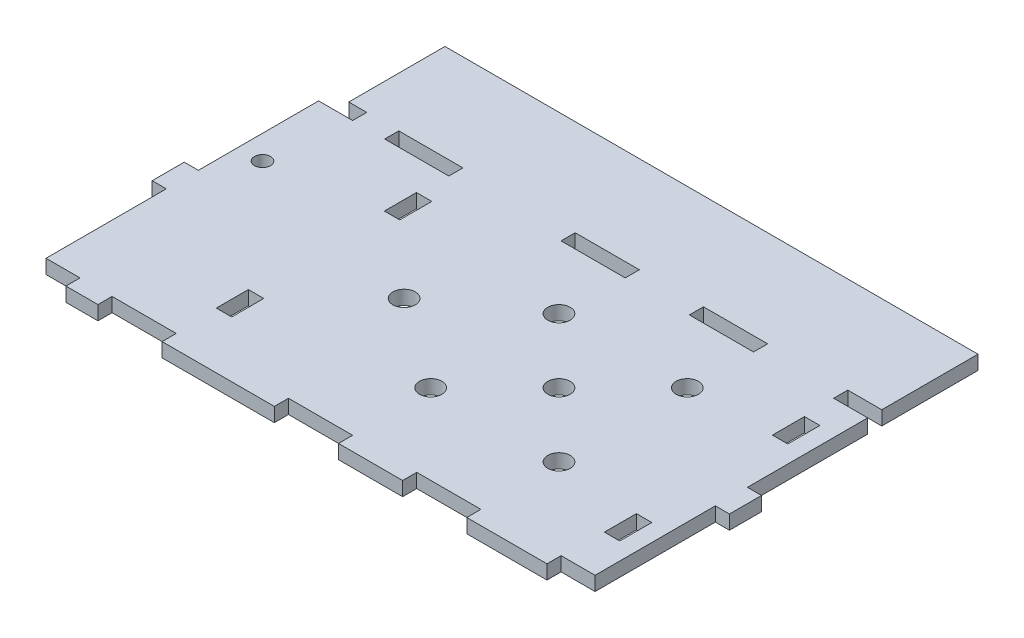
SolidWorks part; units mm, degrees
ref_plane "Front Plane" through (0, 0, 0) normal (0, 0, 1) x (1, 0, 0)
ref_plane "Top Plane" through (0, 0, 0) normal (0, 1, 0) x (1, 0, 0)
ref_plane "Right Plane" through (0, 0, 0) normal (1, 0, 0) x (0, 0, -1)
sketch "Sketch1" plane through (0, 0, 0) normal (0, 1, 0) x (1, 0, 0)
  line L0 (-108.712, 6.35) -> (-114.3, 6.35)
  line L2 (-108.712, -53.975) -> (-108.712, -6.35)
  line L4 (108.712, -53.975) -> (108.712, -6.35)
  line L5 (-108.712, -53.975) -> (108.712, 53.975) construction
  line L6 (-108.712, 53.975) -> (108.712, -53.975) construction
  line L7 (-114.3, 6.35) -> (-114.3, -6.35)
  line L8 (-114.3, -6.35) -> (-108.712, -6.35)
  line L9 (-108.712, 6.35) -> (-108.712, 53.975)
  line L10 (0, 60.325) -> (0, -60.325) construction
  line L11 (114.3, -6.35) -> (108.712, -6.35)
  line L12 (114.3, 6.35) -> (114.3, -6.35)
  line L13 (108.712, 6.35) -> (114.3, 6.35)
  line L14 (108.712, 6.35) -> (108.712, 53.975)
  line L23 (-108.712, 0) -> (106.818, 0) construction
  line L32 (-108.712, 53.975) -> (-95.25, 53.975)
  line L33 (-108.712, -53.975) -> (-95.25, -53.975)
  line L34 (-82.55, 53.975) -> (-57.15, 53.975)
  line L36 (-95.25, 53.975) -> (-95.25, 59.563)
  line L38 (-82.55, 53.975) -> (-82.55, 59.563)
  line L40 (-57.15, 53.975) -> (-57.15, 59.563)
  line L42 (-12.7, 53.975) -> (-12.7, 59.563)
  line L44 (12.7, 53.975) -> (12.7, 59.563)
  line L46 (38.1, 53.975) -> (38.1, 59.563)
  line L48 (63.5, 53.975) -> (63.5, 59.563)
  line L50 (95.25, 53.975) -> (95.25, 59.563)
  line L51 (-12.7, 53.975) -> (12.7, 53.975)
  line L52 (38.1, 53.975) -> (63.5, 53.975)
  line L53 (95.25, 53.975) -> (108.712, 53.975)
  line L54 (95.25, -53.975) -> (95.25, -59.563)
  line L55 (63.5, -59.563) -> (95.25, -59.563)
  line L56 (63.5, -53.975) -> (63.5, -59.563)
  line L57 (38.1, -53.975) -> (38.1, -59.563)
  line L58 (12.7, -59.563) -> (38.1, -59.563)
  line L59 (12.7, -53.975) -> (12.7, -59.563)
  line L60 (-12.7, -53.975) -> (-12.7, -59.563)
  line L61 (-57.15, -59.563) -> (-12.7, -59.563)
  line L62 (-57.15, -53.975) -> (-57.15, -59.563)
  line L63 (-82.55, -53.975) -> (-82.55, -59.563)
  line L64 (-95.25, -59.563) -> (-82.55, -59.563)
  line L65 (-95.25, -53.975) -> (-95.25, -59.563)
  line L66 (-82.55, -53.975) -> (-57.15, -53.975)
  line L67 (-12.7, -53.975) -> (12.7, -53.975)
  line L68 (38.1, -53.975) -> (63.5, -53.975)
  line L69 (95.25, -53.975) -> (108.712, -53.975)
  line L70 (95.25, 59.563) -> (108.712, 59.563)
  line L71 (108.712, 59.563) -> (108.712, 97.663)
  line L72 (-95.25, 59.563) -> (-102.362, 59.563)
  line L73 (-102.362, 59.563) -> (-102.362, 97.663)
  line L74 (-102.362, 97.663) -> (108.712, 97.663)
  line L75 (63.5, 59.563) -> (38.1, 59.563)
  line L76 (12.7, 59.563) -> (-12.7, 59.563)
  line L77 (-57.15, 59.563) -> (-82.55, 59.563)
  point P0 (0, 0)
  dimension "D1" = 107.95
  dimension "D2" = 217.424
  dimension "D3" = 12.7
  dimension "D4" = 5.588
  dimension "D5" = 5.588
  dimension "D6" = 12.7
  dimension "D7" = 25.4
  dimension "D8" = 13.462
  dimension "D9" = 38.1
extrude "Boss-Extrude1" add sketch "Sketch1" along normal blind 5.588
sketch "Sketch9" plane through (0, 5.588, 0) normal (0, 1, 0) x (1, 0, 0)
  line L0 (-108.712, -6.35) -> (-108.712, -53.975) construction
  line L1 (-57.912, -24.638) -> (-51.816, -24.638)
  line L2 (-57.912, -24.638) -> (-57.912, -37.338)
  line L3 (-57.912, -37.338) -> (-51.816, -37.338)
  line L4 (-51.816, -24.638) -> (-51.816, -37.338)
  line L5 (-82.55, -53.975) -> (-57.15, -53.975) construction
  line L6 (-57.912, 29.21) -> (-51.816, 29.21)
  line L7 (-57.912, 29.21) -> (-57.912, 41.91)
  line L8 (-57.912, 41.91) -> (-51.816, 41.91)
  line L9 (-51.816, 29.21) -> (-51.816, 41.91)
  line L10 (95.758, -24.638) -> (101.854, -24.638)
  line L11 (95.758, -24.638) -> (95.758, -37.338)
  line L12 (95.758, -37.338) -> (101.854, -37.338)
  line L13 (101.854, -24.638) -> (101.854, -37.338)
  line L14 (95.758, 41.91) -> (101.854, 41.91)
  line L15 (95.758, 41.91) -> (95.758, 29.21)
  line L16 (95.758, 29.21) -> (101.854, 29.21)
  line L17 (101.854, 41.91) -> (101.854, 29.21)
  line L18 (108.712, -53.975) -> (108.712, -6.35) construction
  line L19 (108.712, 6.35) -> (108.712, 53.975) construction
  dimension "D1" = 12.7
  dimension "D2" = 6.096
  dimension "D3" = 50.8
  dimension "D4" = 16.637
  dimension "D5" = 50.8
  dimension "D6" = 83.185
  dimension "D7" = 12.7
  dimension "D8" = 6.096
  dimension "D9" = 12.7
  dimension "D10" = 6.096
  dimension "D11" = 6.096
  dimension "D12" = 12.7
  dimension "D13" = 6.858
  dimension "D14" = 6.858
extrude "Cut-Extrude1" cut sketch "Sketch9" against normal up to next
sketch "Sketch12" plane through (0, 5.588, 0) normal (0, 1, 0) x (1, 0, 0)
  line L0 (-95.25, 53.975) -> (-108.712, 53.975) construction
  line L1 (-108.712, 53.975) -> (-108.712, 6.35) construction
  circle A0 centre (-99.187, 22.225) radius 3.175
  point P4 (-101.981, 53.975)
  dimension "D1" = 6.35
  dimension "D2" = 31.75
  dimension "D3" = 9.525
extrude "Cut-Extrude2" cut sketch "Sketch12" against normal up to next
sketch "Sketch13" plane through (0, 0, 0) normal (0, -1, 0) x (1, 0, 0)
  line L0 (38.1, -53.975) -> (63.5, -53.975) construction
  circle A0 centre (62.6731, 22.225) radius 4.445
  circle A1 centre (11.8731, 22.225) radius 4.445
  circle A2 centre (11.8731, -28.575) radius 4.445
  circle A3 centre (62.6731, -28.575) radius 4.445
  circle A4 centre (37.2731, -3.175) radius 4.445
  circle A5 centre (-24.0609, -3.175) radius 4.445
  dimension "D1" = 8.89
  dimension "D2" = 50.8
  dimension "D3" = 8.89
  dimension "D4" = 50.8
  dimension "D5" = 50.8
  dimension "D6" = 25.4
  dimension "D7" = 25.4
  dimension "D8" = 25.4
extrude "Cut-Extrude3" cut sketch "Sketch13" against normal up to next
sketch "Sketch14" plane through (0, 5.588, 0) normal (0, 1, 0) x (1, 0, 0)
  line L0 (108.712, -53.975) -> (108.712, -6.35) construction
  line L1 (102.362, -6.35) -> (105.537, -6.35)
  line L2 (102.362, -6.35) -> (102.362, 6.35)
  line L3 (102.362, 6.35) -> (105.537, 6.35)
  line L4 (105.537, -6.35) -> (105.537, 6.35)
  line L5 (108.712, -6.35) -> (114.3, -6.35) construction
  dimension "D1" = 3.175
  dimension "D2" = 12.7
  dimension "D3" = 3.175
